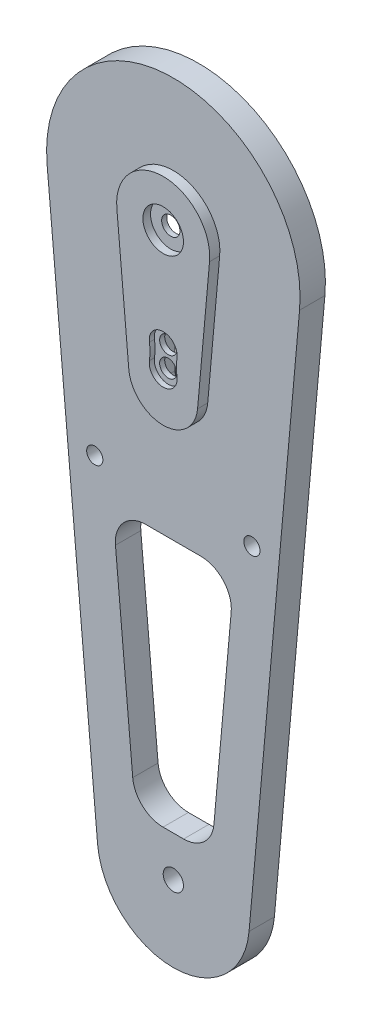
SolidWorks part; units mm, degrees
material "PLA"
ref_plane "Alzado" through (0, 0, 0) normal (0, 0, 1) x (1, 0, 0)
ref_plane "Planta" through (0, 0, 0) normal (0, 1, 0) x (1, 0, 0)
ref_plane "Vista lateral" through (0, 0, 0) normal (1, 0, 0) x (0, 0, -1)
other "PLA"
sketch "Croquis1" plane through (0, 0, 0) normal (0, 0, 1) x (1, 0, 0)
  line L0 (0, 112) -> (0, 0) construction
  line L1 (-14.9401, -1.3393) -> (-25.1002, 112)
  line L2 (14.9401, -1.3393) -> (24.9002, 109.7679)
  line L3 (0, 119.505) -> (19.4147, 119.505) construction
  line L4 (-3.65, 83.155) -> (-3.65, 101.0409)
  line L5 (3.65, 83.155) -> (3.65, 101.0409)
  line L11 (0, 112) -> (0, 123.4883) construction
  line L12 (0.5, 119.4883) -> (0.5, 119.505)
  arc A0 (-14.9401, -1.3393) -> (14.9401, -1.3393) centre (0, 0) ccw
  arc A1 (24.9002, 109.7679) -> (-24.9002, 109.7679) centre (0, 112) ccw
  circle A2 centre (0, 112) radius 7.505
  circle A3 centre (0, 0) radius 2
  circle A4 centre (0, 112) radius 1.75
  arc A5 (0, 79.505) -> (-3.65, 83.155) centre (0, 83.155) cw
  arc A6 (-5.8522, 107.3014) -> (-3.65, 101.0409) centre (-13.65, 101.0409) cw
  arc A7 (5.8522, 107.3014) -> (3.65, 101.0409) centre (13.65, 101.0409) ccw
  arc A8 (0, 79.505) -> (3.65, 83.155) centre (0, 83.155) ccw
  point P26 (0, 79.4404)
  dimension "D1" = 30
  dimension "D2" = 50
  dimension "D4" = 15.01
  dimension "D5" = 4
  dimension "D6" = 3.5
  dimension "D7" = 10
  dimension "D3" = 112
  dimension "D8" = 40
  dimension "D9" = 7.3
extrude "Saliente-Extruir1" add sketch "Croquis1" along normal blind 5 contours L2 A1 L1 A0 A2 A3 | A0 region at (0, 64.8615, 0)
ref_plane "Plano1" through (0, 0, 0) normal (1, 0, 0) x (0, -1, 0)
sketch "Croquis11" plane through (0, 0, 0) normal (0, 0, -1) x (-1, 0, 0)
  line L2 (0, 0) -> (0, 137) construction
  line L3 (-10.6804, 11.0037) -> (-15.5, 64.7681) construction
  line L4 (-14.9401, -1.3393) -> (-24.9002, 109.7679) construction
  arc A2 (24.9002, 109.7679) -> (-24.9002, 109.7679) centre (0, 112) ccw construction
  circle A3 centre (-15.5, 64.7681) radius 1.6
  circle A4 centre (15.5, 64.7681) radius 1.6
  dimension "D1" = 31
extrude "Cortar-Extruir1" cut sketch "Croquis11" against normal blind 6 contours A3 | A4
sketch "Croquis12" plane through (0, 0, 5) normal (0, 0, 1) x (1, 0, 0)
  line L0 (0, 79.5266) -> (0, 0) construction
  line L1 (-12, 58) -> (12, 58)
  line L2 (12, 58) -> (7.5178, 8)
  line L3 (7.5178, 8) -> (-7.5178, 8)
  line L4 (-12, 58) -> (-7.5178, 8)
  line L5 (14.9401, -1.3393) -> (24.9002, 109.7679) construction
  point P8 (0, 8)
  point P9 (0, 58)
  dimension "D1" = 24
  dimension "D2" = 50
  dimension "D3" = 8
extrude "Cortar-Extruir2" cut sketch "Croquis12" against normal up to next contours L4 | L0 L3 | L0 L3 | L2 | L1 L0 | L0 L1 region at (0, 34.9137, 5)
sketch "Croquis13" plane through (0, 0, 5) normal (0, 0, 1) x (1, 0, 0)
  line L0 (0, 137) -> (0, -15) construction
  line L2 (6.7847, 84.8645) -> (9.1438, 111.1803)
  line L3 (-6.7847, 84.8645) -> (-9.1438, 111.1803)
  line L4 (14.9401, -1.3393) -> (24.9002, 109.7679) construction
  arc A0 (-9.1438, 111.1803) -> (9.1438, 111.1803) centre (0, 112) ccw
  arc A2 (24.9002, 109.7679) -> (-24.9002, 109.7679) centre (0, 112) ccw construction
  arc A3 (-14.9401, -1.3393) -> (14.9401, -1.3393) centre (0, 0) ccw construction
  arc A4 (-9.1438, 111.1803) -> (9.1438, 111.1803) centre (0, 112) cw
  arc A5 (5.8522, 107.3014) -> (-5.8522, 107.3014) centre (0, 112) ccw construction
  arc A6 (6.7847, 84.8645) -> (-6.7847, 84.8645) centre (0, 85.4727) cw
  circle A7 centre (0, 112) radius 4
  circle A8 centre (0, 112) radius 1.8
  dimension "D1" = 8
  dimension "D2" = 3.6
extrude "Saliente-Extruir2" add sketch "Croquis13" along normal blind 2 contours A6 L3 A4 L2 | A8
extrude "Saliente-Extruir3" add sketch "Croquis13<3>" against normal blind 0.5 contours L0 A7 | A7 | A8 region at (-3.8869, 112, 5)
sketch "Croquis13<3>" plane through (0, 0, 5) normal (0, 0, 1) x (1, 0, 0) same geometry as "Croquis13"
sketch "Croquis14" plane through (0, 0, 7) normal (0, 0, 1) x (1, 0, 0)
  circle A0 centre (0, 112) radius 4
  dimension "D1" = 8
extrude "Cortar-Extruir3" cut sketch "Croquis14" against normal blind 1.5
chamfer "Chaflán1" distance 1 angle 45 6 edges at (0, 79.505, 0) (-3.65, 92.0979, 0) (3.65, 92.0979, 0) (4.2166, 104.3592, 0) (-4.2166, 104.3592, 0) (0, 119.505, 0)
sketch "Croquis15" plane through (0, 0, 5) normal (0, 0, -1) x (-1, 0, 0)
  line L0 (0, 137) -> (0, -15) construction
  arc A0 (24.9002, 109.7679) -> (-24.9002, 109.7679) centre (0, 112) ccw construction
  arc A1 (-14.9401, -1.3393) -> (14.9401, -1.3393) centre (0, 0) ccw construction
  circle A2 centre (0, 87.915) radius 1.45
  circle A3 centre (0, 91.915) radius 1.45
  arc A4 (-3.65, 83.155) -> (3.65, 83.155) centre (0, 83.155) ccw construction
  circle A5 centre (0, 91.915) radius 0.75
  circle A6 centre (0, 87.915) radius 0.75
  point P15 (0, 79.505)
  dimension "D1" = 8.41
  dimension "D3" = 2.9
  dimension "D4" = 1.5
  dimension "D2" = 4
hole_wizard "Refrentado para tornillo con cabeza troncocónica de M31" positions "Croquis16" profile "Croquis17" counterbore size "M3" standard "Ansi Metric" end condition up to next
sketch "Croquis16" plane through (0, 0, 7) normal (0, 0, -1) x (-1, 0, 0)
  point P0 (0, 91.915)
  point P3 (0, 87.915)
sketch "Croquis17" plane through (0, 91.915, 7) normal (1, 0, 0) x (0, -1, 0)
  line L0 (0, 0) -> (0, 2)
  line L1 (0, 2) -> (1.7, 2)
  line L3 (1.7, 2) -> (1.7, 1)
  line L4 (1.7, 1) -> (2.75, 1)
  line L5 (2.75, 1) -> (2.75, 0)
  line L7 (2.75, 0) -> (0, 0)
  line L11 (0, -6.35) -> (0, 107.95) construction
  dimension "Diámetro de taladro hasta el siguiente" = 3.4
  dimension "Profundidad de taladro hasta el siguiente" = 2
  dimension "Diámetro de refrentado" = 5.5
  dimension "Profundidad de refrentado" = 1
fillet "Redondeo1" radius 10 2 edges at (-1.8875, 89.915, 6.5) (1.8875, 89.915, 6.5)
fillet "Redondeo2" radius 6 4 edges at (7.5178, 8, 2.5) (-7.5178, 8, 2.5) (12, 58, 2.5) (-12, 58, 2.5)
